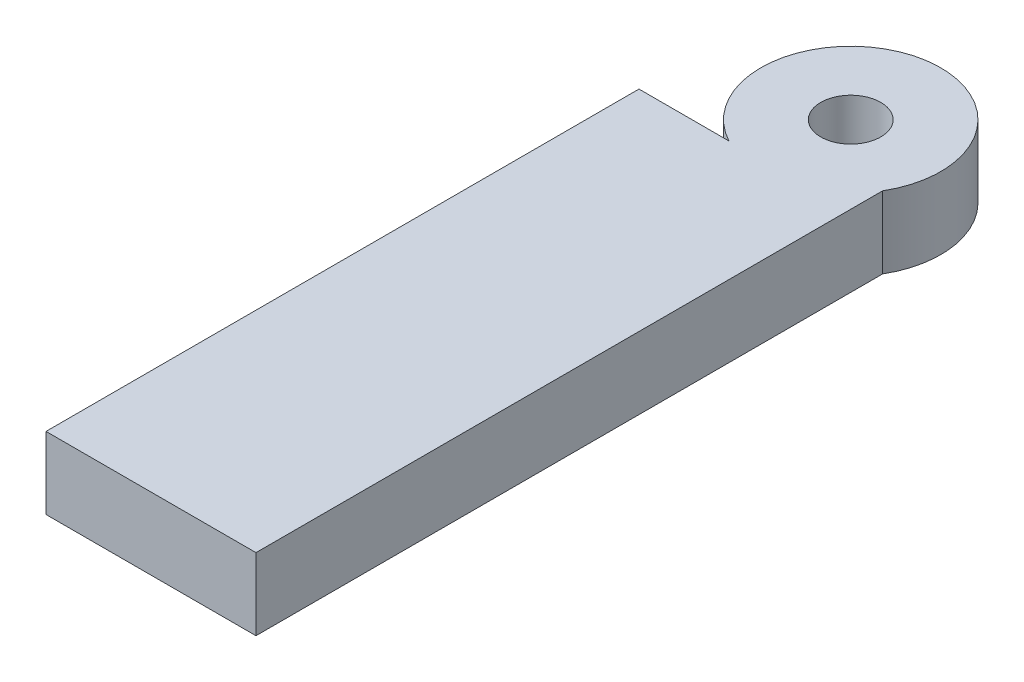
SolidWorks part; units mm, degrees
ref_plane "Front Plane" through (0, 0, 0) normal (0, 0, 1) x (1, 0, 0)
ref_plane "Top Plane" through (0, 0, 0) normal (0, 1, 0) x (1, 0, 0)
ref_plane "Right Plane" through (0, 0, 0) normal (1, 0, 0) x (0, 0, -1)
sketch "Sketch1" plane through (0, 0, 0) normal (0, 1, 0) x (1, 0, 0)
  line L0 (0, 9.525) -> (-4.4901, 5.0349)
  line L1 (0, 9.525) -> (0, 0) construction
  line L2 (-4.4901, -71.1651) -> (8.2099, -71.1651)
  line L3 (-4.4901, 5.0349) -> (-4.4901, -71.1651)
  line L4 (8.2099, -71.1651) -> (8.2099, -4.8295)
  circle A0 centre (0, 0) radius 3.175
  circle A1 centre (0, 0) radius 9.525
  dimension "D1" = 6.35
  dimension "D2" = 19.05
  dimension "D3" = 45
  dimension "D4" = 6.35
  dimension "D5" = 76.2
  dimension "D6" = 12.7
extrude "Boss-Extrude1" add sketch "Sketch1" along normal blind 7.62 contours L0 A1 | A1 A0 L0 | A1 L0 L3 region at (6.568, 0, -6.568) region at (-6.1109, 0, -0.9585) region at (1.9114, 0, 39.8268)
sketch "Sketch2" plane through (-4.4901, 0, 0) normal (-1, 0, 0) x (0, 0, 1)
  line L1 (8.4003, 7.62) -> (71.1651, 7.62) construction
  line L2 (8.4003, 7.62) -> (8.4003, 0) construction
  circle A0 centre (14.7503, 3.81) radius 1.27
  circle A1 centre (52.8503, 3.81) radius 1.27
  dimension "D1" = 2.54
  dimension "D2" = 2.54
  dimension "D3" = 6.35
  dimension "D4" = 3.81
  dimension "D5" = 38.1
extrude "Cut-Extrude1" cut sketch "Sketch2" against normal blind 6.35
sketch "Sketch3" plane through (-4.4901, 0, 0) normal (-1, 0, 0) x (0, 0, 1)
  line L4 (8.4003, 0) -> (71.1651, 0)
  line L5 (71.1651, 0) -> (71.1651, 7.62)
  line L6 (71.1651, 7.62) -> (8.4003, 7.62)
  line L7 (8.4003, 7.62) -> (8.4003, 0)
  line L8 (8.4003, 0) -> (71.1651, 0)
  line L9 (71.1651, 0) -> (71.1651, 7.62)
  line L10 (71.1651, 7.62) -> (8.4003, 7.62)
  line L12 (8.4003, 7.62) -> (8.4003, 0)
  circle A0 centre (52.8503, 3.81) radius 1.27 construction
  circle A1 centre (14.7503, 3.81) radius 1.27 construction
  circle A2 centre (52.8503, 3.81) radius 1.27
  circle A3 centre (14.7503, 3.81) radius 1.27
  dimension "D1" = 0
extrude "Boss-Extrude2" add sketch "Sketch3" along normal blind 9.525
sketch "Sketch4" [suppressed] plane through (-17.9605, 0, 0) normal (-1, 0, 0) x (0, 0, 1)
  line L4 (8.4355, 0) -> (59.2355, 0)
  line L5 (59.2355, 0) -> (59.2355, 7.62)
  line L6 (59.2355, 7.62) -> (8.4355, 7.62)
  line L7 (8.4355, 7.62) -> (8.4355, 0)
  line L8 (8.4355, 0) -> (59.2355, 0)
  line L9 (59.2355, 0) -> (59.2355, 7.62)
  line L10 (59.2355, 7.62) -> (8.4355, 7.62)
  line L11 (8.4355, 7.62) -> (8.4355, 0)
  circle A0 centre (52.8855, 3.81) radius 1.27 construction
  circle A1 centre (14.7855, 3.81) radius 1.27 construction
  circle A2 centre (52.8855, 3.81) radius 1.27
  circle A3 centre (14.7855, 3.81) radius 1.27
  dimension "D1" = 0
extrude "Boss-Extrude3" [suppressed] add sketch "Sketch4" along normal blind 4.7625
